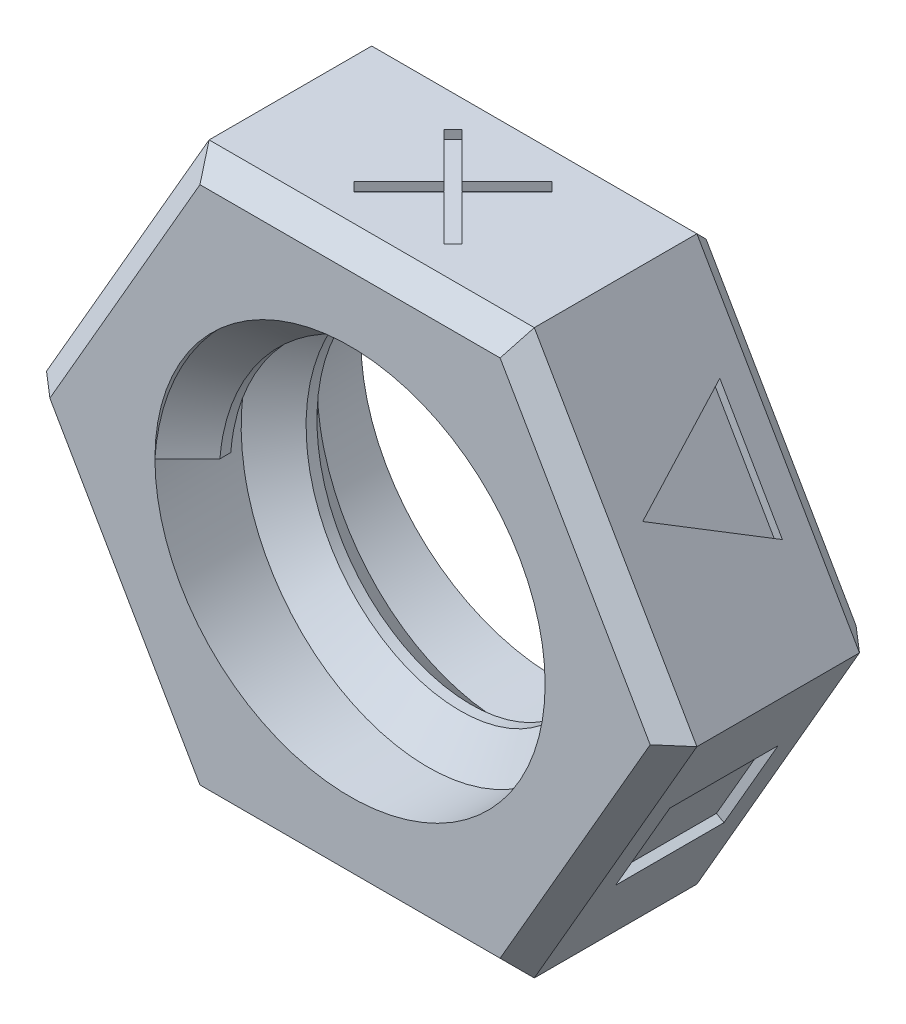
SolidWorks part; units mm, degrees
ref_plane "前视基准面" through (0, 0, 0) normal (0, 0, 1) x (1, 0, 0)
ref_plane "上视基准面" through (0, 0, 0) normal (0, 1, 0) x (1, 0, 0)
ref_plane "右视基准面" through (0, 0, 0) normal (1, 0, 0) x (0, 0, -1)
sketch "草图1" plane through (0, 0, 0) normal (0, 0, 1) x (1, 0, 0)
  line L1 (15, 0) -> (7.5, 12.9904)
  line L2 (7.5, 12.9904) -> (-7.5, 12.9904)
  line L3 (-7.5, 12.9904) -> (-15, 0)
  line L4 (-15, 0) -> (-7.5, -12.9904)
  line L5 (-7.5, -12.9904) -> (7.5, -12.9904)
  line L6 (7.5, -12.9904) -> (15, 0)
  circle A0 centre (0, 0) radius 15
  circle A1 centre (0, 0) radius 12.9904 construction
  dimension "D1" = 30
extrude "凸台-拉伸1" add sketch "草图1" along normal blind 9.5 contours L2 L3 L4 L5 L6 L1
sketch "草图2" plane through (0, 0, 0) normal (0, 0, -1) x (-1, 0, 0)
  circle A0 centre (0, 0) radius 7
  circle A1 centre (0, 0) radius 9
  dimension "D1" = 14
  dimension "D2" = 2
sketch "草图3" plane through (0, 0, 0) normal (0, 0, -1) x (-1, 0, 0)
  circle A0 centre (0, 0) radius 9 construction
  circle A1 centre (0, 0) radius 9
extrude "切除-拉伸1" cut sketch "草图3" against normal blind 10
ref_plane "基准面1" through (0, 0, 1.75) normal (0, 0, 1) x (1, 0, 0)
sketch "草图4" plane through (0, 0, 1.75) normal (0, 0, 1) x (1, 0, 0)
  circle A0 centre (0, 0) radius 9 construction
  circle A1 centre (0, 0) radius 9
curve "螺旋线/涡状线1" pitch 4 height 6 radius 9 centre (0, 0, 1.75) axis (0, 0, 1) start towards (1, 0, 0)
sketch "草图5" plane through (0, 0, 0) normal (0, 1, 0) x (1, 0, 0)
  line L0 (9, 0) -> (9, -3.5)
  line L4 (9, 0) -> (7.5, -1.5)
  line L5 (7.5, -1.5) -> (7.5, -2)
  line L6 (7.5, -2) -> (9, -3.5)
  point P2 (9, -1.75)
  dimension "D1" = 3.5
  dimension "D2" = 1.5
  dimension "D3" = 45
  dimension "D4" = 45
sweep "扫描1" add profiles "草图5" path "螺旋线/涡状线1"
chamfer "倒角1" distance 1 angle 45 12 edges at (0, -12.9904, 0) (11.25, -6.4952, 0) (11.25, 6.4952, 0) (0, 12.9904, 0) (-11.25, 6.4952, 0) (-11.25, -6.4952, 0) (-11.25, -6.4952, 9.5) (0, -12.9904, 9.5) (11.25, -6.4952, 9.5) (11.25, 6.4952, 9.5) (0, 12.9904, 9.5) (-11.25, 6.4952, 9.5)
sketch "草图7" plane through (11.25, 6.4952, 0) normal (0.866, 0.5, 0) x (0, 0, -1)
  line L0 (-8.5, 0) -> (-1, 0) construction
  line L8 (-2.25, 2.8868) -> (-7.25, 0)
  line L9 (-7.25, 0) -> (-2.25, -2.8868)
  line L10 (-2.25, -2.8868) -> (-2.25, 2.8868)
  line L11 (-7.25, 0) -> (-2.25, 0) construction
  line L12 (-8.5, 7.5) -> (-8.5, -7.5) construction
  line L13 (-1, -7.5) -> (-1, 7.5) construction
  line L14 (-4.75, 0) -> (-4.75, -2.4501) construction
  point P12 (-4.75, 0)
  dimension "D1" = 5
extrude "切除-拉伸3" cut sketch "草图7" against normal blind 0.4
sketch "草图10" plane through (0, 12.9904, 0) normal (0, 1, 0) x (1, 0, 0)
  line L0 (0, -1) -> (0, -8.5) construction
  line L1 (7.5, -1) -> (-7.5, -1) construction
  line L2 (-7.5, -8.5) -> (7.5, -8.5) construction
  line L3 (-2.5, -2.25) -> (2.5, -7.25) construction
  line L4 (2.5, -7.25) -> (-2.5, -7.25)
  line L5 (2.5, -7.25) -> (2.5, -2.25)
  line L6 (2.5, -2.25) -> (-2.5, -2.25)
  line L7 (-2.5, -7.25) -> (-2.5, -2.25)
  line L8 (0, -2.25) -> (0, -7.25) construction
  line L9 (2.5, -4.75) -> (-2.5, -4.75) construction
  line L10 (2.5, -2.25) -> (-2.5, -7.25) construction
  line L11 (2.0757, -2.25) -> (-2.5, -6.8257)
  line L12 (-2.5, -2.6743) -> (2.0757, -7.25)
  line L13 (2.5, -2.6743) -> (-2.0757, -7.25)
  line L14 (-2.0757, -2.25) -> (2.5, -6.8257)
  line L15 (-2.2879, -2.0379) -> (2.7121, -7.0379) construction
  line L16 (-2.7121, -2.4621) -> (2.2879, -7.4621) construction
  line L17 (2.2879, -2.0379) -> (-2.7121, -7.0379) construction
  line L18 (2.7121, -2.4621) -> (-2.2879, -7.4621) construction
  line L19 (-2.5, -2.6743) -> (-2.0757, -2.25)
  line L20 (2.0757, -2.25) -> (2.5, -2.6743)
  line L21 (-2.5, -6.8257) -> (-2.0757, -7.25)
  line L22 (2.0757, -7.25) -> (2.5, -6.8257)
  point P6 (0, -4.75)
  dimension "D1" = 5
  dimension "D2" = 0.3
  dimension "D3" = 0.3
sketch "草图11" plane through (11.25, -6.4952, 0) normal (0.866, -0.5, 0) x (0, 0, -1)
  line L0 (-8.5, 0) -> (-1, 0) construction
  line L1 (-8.5, 7.5) -> (-8.5, -7.5) construction
  line L2 (-1, -7.5) -> (-1, 7.5) construction
  line L4 (-2.25, -2.5) -> (-7.25, -2.5)
  line L5 (-2.25, -2.5) -> (-2.25, 2.5)
  line L6 (-2.25, 2.5) -> (-7.25, 2.5)
  line L7 (-7.25, -2.5) -> (-7.25, 2.5)
  line L8 (-4.75, 2.5) -> (-4.75, -2.5) construction
  line L9 (-2.25, 0) -> (-7.25, 0) construction
  point P6 (-4.75, 0)
  dimension "D1" = 5
sketch "草图12" plane through (-11.25, 6.4952, 0) normal (-0.866, 0.5, 0) x (0, 0, 1)
  line L0 (1, 0) -> (8.5, 0) construction
  line L1 (1, 7.5) -> (1, -7.5) construction
  line L2 (8.5, -7.5) -> (8.5, 7.5) construction
  circle A0 centre (4.75, 0) radius 2.5
  dimension "D1" = 5
extrude "切除-拉伸4" cut sketch "草图12" against normal blind 0.4 contours A0
extrude "切除-拉伸6" cut sketch "草图10" against normal blind 0.4 and the other way through all contours L14 L6 L7 L12 L11 | L11 L14 L13 L5 L6 | L13 L12 L11 L7 L4 | L14 L13 L12 L4 L5 | L14 L11 L12 L13 region at (1.25, 12.9904, 6) region at (-1.25, 12.9904, 6) region at (0, 12.9904, 4.75) region at (1.25, 12.9904, 3.5) region at (-1.25, 12.9904, 3.5)
extrude "切除-拉伸7" cut sketch "草图11" against normal blind 0.4 contours L7 L6 L5 L4
